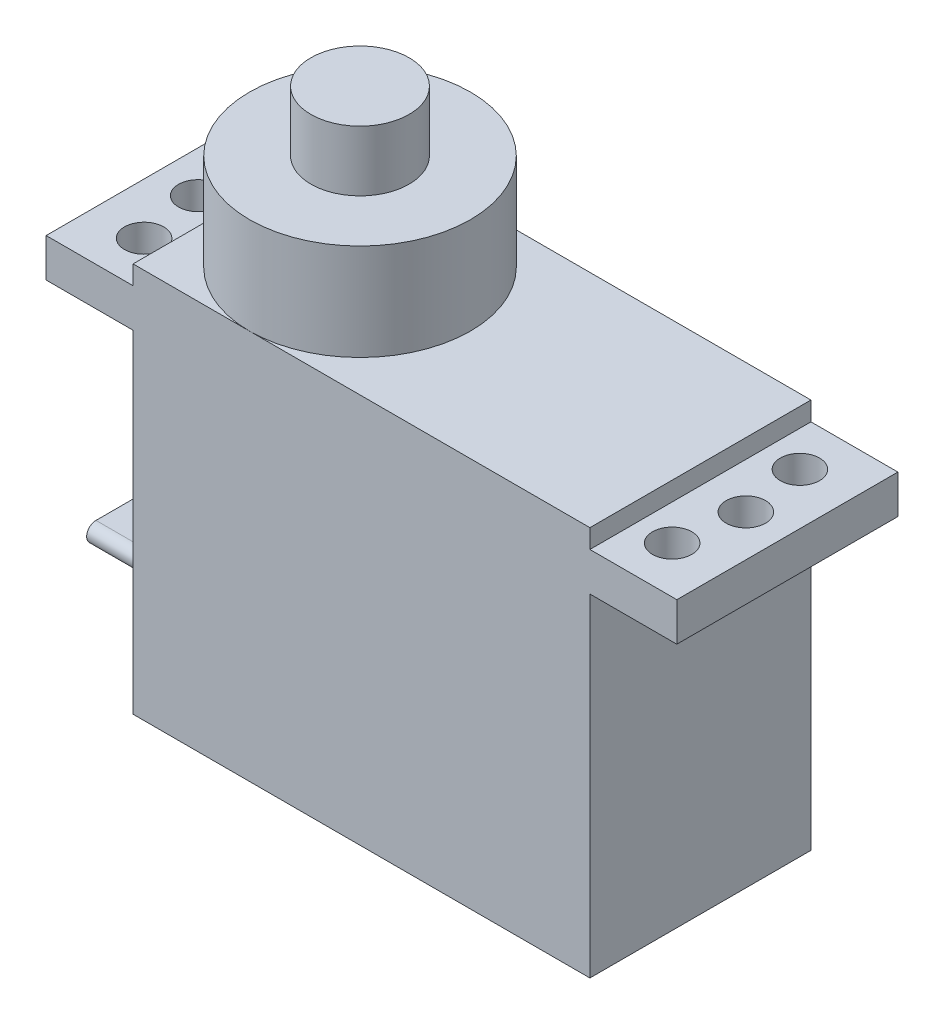
SolidWorks part; units mm, degrees
material "CA"
ref_plane "Front Plane" through (0, 0, 0) normal (0, 0, 1) x (1, 0, 0)
ref_plane "Top Plane" through (0, 0, 0) normal (0, 1, 0) x (1, 0, 0)
ref_plane "Right Plane" through (0, 0, 0) normal (1, 0, 0) x (0, 0, -1)
sketch "Sketch1" plane through (0, 0, 0) normal (0, 0, 1) x (1, 0, 0)
  line L2 (-11.811, 20.1676) -> (-11.811, 0)
  line L3 (-11.811, 0) -> (11.811, 0)
  line L4 (11.811, 20.1676) -> (11.811, 0)
  line L5 (-11.811, 20.1676) -> (11.811, 20.1676)
  point P0 (0, 0)
  dimension "D1" = 23.622
  dimension "D2" = 20.1676
extrude "Boss-Extrude1" add sketch "Sketch1" along normal mid plane 11.43
sketch "Sketch4" plane through (-11.811, 0, 0) normal (-1, 0, 0) x (0, 0, 1)
  line L0 (-5.715, 20.1676) -> (-5.715, 0) construction
  line L1 (-5.715, 19.1897) -> (5.715, 19.1897)
  line L2 (-5.715, 19.1897) -> (-5.715, 17.1958)
  line L3 (-5.715, 17.1958) -> (5.715, 17.1958)
  line L4 (5.715, 19.1897) -> (5.715, 17.1958)
  line L5 (5.715, 20.1676) -> (5.715, 0) construction
  line L7 (5.715, 0) -> (-5.715, 0) construction
  dimension "D1" = 1.9939
  dimension "D2" = 17.1958
extrude "Boss-Extrude4" add sketch "Sketch4" along normal blind 4.4958
mirror "Mirror1" about plane through (0, 0, 0) normal (1, 0, 0) of "Boss-Extrude4"
sketch "Sketch5" plane through (0, 20.1676, 0) normal (0, 1, 0) x (1, 0, 0)
  line L0 (-11.0922, 0) -> (11.0922, 0) construction
  line L1 (11.811, 5.715) -> (-11.811, 5.715) construction
  line L3 (-11.811, -5.715) -> (-11.811, 5.715) construction
  circle A0 centre (-5.7912, 0) radius 5.715
  dimension "D1" = 6.0198
extrude "Boss-Extrude5" add sketch "Sketch5" along normal blind 5.969 from surface starting at face at (-14.0589, 19.1897, 0)
sketch "Sketch6" plane through (0, 25.1587, 0) normal (0, 1, 0) x (1, 0, 0)
  line L1 (-11.811, -5.715) -> (-11.811, 5.715) construction
  circle A0 centre (-5.7912, 0) radius 2.54
  dimension "D1" = 6.0198
  dimension "D2" = 5.08
extrude "Boss-Extrude6" add sketch "Sketch6" along normal blind 3.1242
sketch "Sketch7" plane through (0, 19.1897, 0) normal (0, 1, 0) x (1, 0, 0)
  line L0 (-15.5556, 0) -> (15.5556, 0) construction
  circle A0 centre (-13.6525, 3.302) radius 1.016
  circle A1 centre (-13.6525, -3.302) radius 1.016
  circle A2 centre (-14.1605, 0) radius 1.016
  dimension "D1" = 13.6525
  dimension "D3" = 2.032
  dimension "D5" = 14.1605
  dimension "D6" = 2.032
  dimension "D2" = 3.302
  dimension "D4" = 6.604
extrude "Cut-Extrude1" cut sketch "Sketch7" against normal through all
mirror "Mirror2" about plane through (0, 0, 0) normal (1, 0, 0) of "Cut-Extrude1"
sketch "Sketch8" plane through (-11.811, 0, 0) normal (-1, 0, 0) x (0, 0, 1)
  line L0 (5.715, 0) -> (-5.715, 0) construction
  line L1 (-3.0226, 1.524) -> (3.0226, 1.524)
  line L2 (-3.0226, 1.524) -> (-3.0226, 4.826)
  line L3 (-3.0226, 4.826) -> (3.0226, 4.826)
  line L4 (3.0226, 1.524) -> (3.0226, 4.826)
  point P6 (0, 1.524)
  dimension "D1" = 1.524
  dimension "D2" = 3.302
  dimension "D3" = 6.0452
extrude "Boss-Extrude7" add sketch "Sketch8" along normal blind 1.4097
sketch "Sketch9" plane through (-13.2207, 0, 0) normal (-1, 0, 0) x (0, 0, 1)
  line L0 (1.651, 3.175) -> (-1.651, 3.175) construction
  line L1 (1.651, 2.6924) -> (-1.651, 2.6924)
  line L2 (1.651, 3.6576) -> (-1.651, 3.6576)
  line L3 (3.0226, 1.524) -> (3.0226, 4.826) construction
  arc A0 (1.651, 2.6924) -> (1.651, 3.6576) centre (1.651, 3.175) ccw
  arc A1 (-1.651, 3.6576) -> (-1.651, 2.6924) centre (-1.651, 3.175) ccw
  point P2 (0, 3.175)
  point P12 (3.0226, 3.175)
  dimension "D1" = 0.9652
  dimension "D2" = 3.302
extrude "Boss-Extrude8" add sketch "Sketch9" along normal blind 4.572
ref_axis "Axis1" through (-5.7912, 25.1587, 0) along (0, -1, 0)
